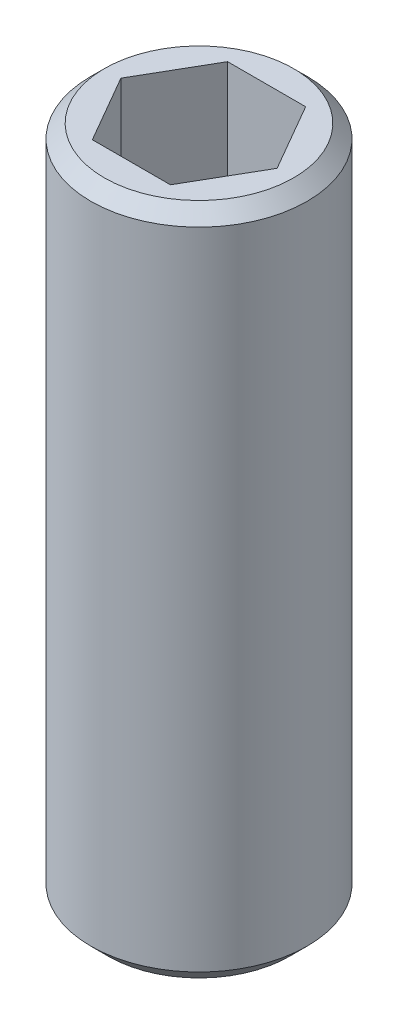
SolidWorks part; units mm, degrees
material "1023 Carbon Steel Sheet (SS)"
ref_plane "Front Plane" through (0, 0, 0) normal (0, 0, 1) x (1, 0, 0)
ref_plane "Top Plane" through (0, 0, 0) normal (0, 1, 0) x (1, 0, 0)
ref_plane "Right Plane" through (0, 0, 0) normal (1, 0, 0) x (0, 0, -1)
sketch "Sketch1" plane through (0, 0, 0) normal (0, 1, 0) x (1, 0, 0)
  circle A0 centre (0, 0) radius 4
  dimension "D1" = 8
extrude "Boss-Extrude1" add sketch "Sketch1" along normal blind 25
cosmetic thread "Cosmetic Thread1" parameters "D1"=25, "D2"=6.619
hole_wizard "Ø5.0mm Dowel Hole1" positions "Sketch3" profile "Sketch4" hole size "Ø5.0" standard "ISO"
sketch "Sketch3" plane through (0, 25, 0) normal (0, 1, 0) x (1, 0, 0)
  point P0 (0, 0)
sketch "Sketch4" plane through (0, 25, 0) normal (1, 0, 0) x (0, 0, 1)
  line L0 (0, 0) -> (0, 7.5022)
  line L1 (0, 7.5022) -> (2.5, 6)
  line L2 (2.5, 6) -> (2.5, 0)
  line L5 (2.5, 0) -> (0, 0)
  line L10 (0, 7.5022) -> (-2.5, 6) construction
  line L11 (0, -6.35) -> (0, 107.95) construction
  dimension "Hole Dia." = 5
  dimension "Hole Depth" = 6
  dimension "Drill Angle" = 118
sketch "Sketch2" plane through (0, 25, 0) normal (0, 1, 0) x (1, 0, 0)
  line L1 (2.8868, 0) -> (1.4434, 2.5)
  line L2 (1.4434, 2.5) -> (-1.4434, 2.5)
  line L3 (-1.4434, 2.5) -> (-2.8868, 0)
  line L4 (-2.8868, 0) -> (-1.4434, -2.5)
  line L5 (-1.4434, -2.5) -> (1.4434, -2.5)
  line L6 (1.4434, -2.5) -> (2.8868, 0)
  circle A0 centre (0, 0) radius 2.5 construction
  point P1 (0, 0)
  dimension "D1" = 5
extrude "Cut-Extrude1" cut sketch "Sketch2" against normal blind 6 contours L3 L4 L5 L6 L1 L2
chamfer "Chamfer1" distance 0.5 angle 45 1 edges at (0, 25, 4)
chamfer "Chamfer2" distance 0.65 angle 45 1 edges at (0, 0, 4)
